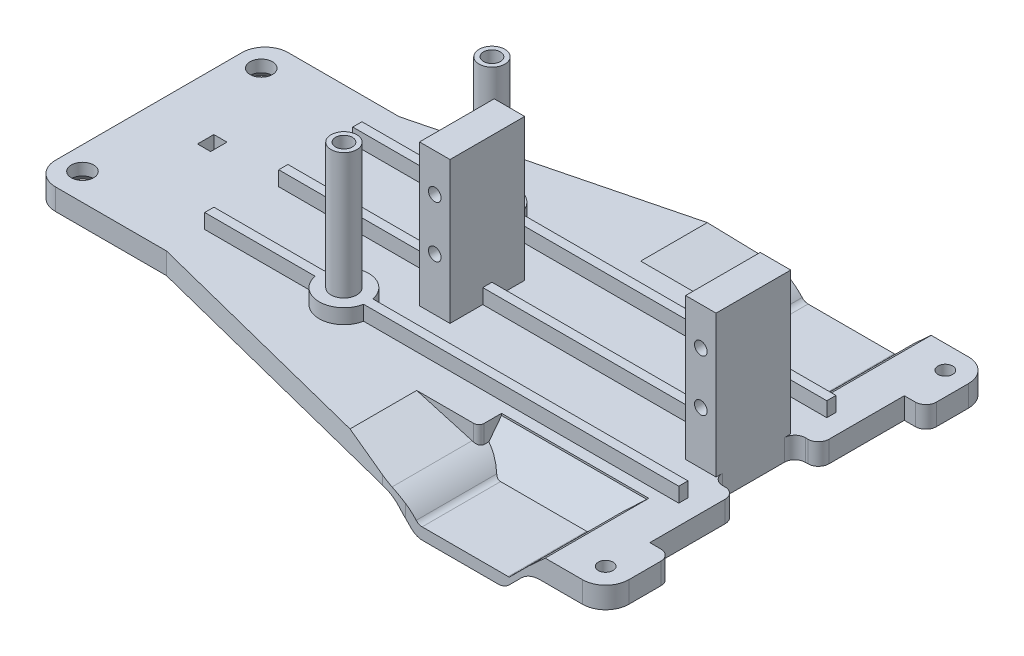
SolidWorks part; units mm, degrees
ref_plane "Front Plane" through (0, 0, 0) normal (0, 0, 1) x (1, 0, 0)
ref_plane "Top Plane" through (0, 0, 0) normal (0, 1, 0) x (1, 0, 0)
ref_plane "Right Plane" through (0, 0, 0) normal (1, 0, 0) x (0, 0, -1)
sketch "Sketch1" plane through (0, 0, 0) normal (0, 1, 0) x (1, 0, 0)
  line L0 (0, 0) -> (0, 17.725)
  line L1 (4.4, 22.125) -> (25.5, 22.125)
  line L2 (25.5, 22.125) -> (83, 36.7)
  line L3 (83, 36.7) -> (119.2, 36.7)
  line L4 (123.6, 32.3) -> (123.6, 26.2)
  line L5 (121.6, 24.2) -> (119.5, 24.2)
  line L6 (119.5, 24.2) -> (119.5, 9.875)
  line L7 (117.5, 7.875) -> (117, 7.875)
  line L8 (115, 5.875) -> (115, 0)
  line L9 (115, 0) -> (0, 0)
  arc A0 (0, 17.725) -> (4.4, 22.125) centre (4.4, 17.725) cw
  arc A1 (119.2, 36.7) -> (123.6, 32.3) centre (119.2, 32.3) cw
  arc A2 (119.5, 9.875) -> (117.5, 7.875) centre (117.5, 9.875) cw
  arc A3 (117, 7.875) -> (115, 5.875) centre (117, 5.875) ccw
  arc A4 (123.6, 26.2) -> (121.6, 24.2) centre (121.6, 26.2) cw
  dimension "D1" = 4.4
  dimension "D3" = 36.7
  dimension "D8" = 2
  dimension "D2" = 123.6
  dimension "D4" = 115
  dimension "D5" = 119.5
  dimension "D6" = 7.875
  dimension "D7" = 24.2
  dimension "D9" = 22.125
  dimension "D10" = 25.5
  dimension "D11" = 83
extrude "Boss-Extrude1" add sketch "Sketch1" along normal blind 4.06
sketch "Sketch2" plane through (0, 0, -36.7) normal (0, 0, -1) x (-1, 0, 0)
  line L0 (-107.5645, -1.4645) -> (-105.2176, -3.8113)
  line L1 (-119.2, 0) -> (-83, 0) construction
  line L2 (-103.0963, -4.69) -> (-88.8, -4.69)
  line L3 (-86.6787, -3.8113) -> (-84.3318, -1.4645)
  line L4 (-95.9481, -4.69) -> (-95.9481, 0) construction
  line L5 (-111.1, 0) -> (-80.7963, 0)
  line L6 (-123.6, 4.06) -> (-123.6, 0) construction
  line L7 (-119.2, 4.06) -> (-83, 4.06) construction
  line L8 (-83, 0) -> (-25.5, 0) construction
  arc A0 (-84.3318, -1.4645) -> (-80.7963, 0) centre (-80.7963, -5) cw
  arc A1 (-107.5645, -1.4645) -> (-111.1, 0) centre (-111.1, -5) ccw
  arc A2 (-88.8, -4.69) -> (-86.6787, -3.8113) centre (-88.8, -1.69) ccw
  arc A3 (-105.2176, -3.8113) -> (-103.0963, -4.69) centre (-103.0963, -1.69) ccw
  point P11 (-84.0806, 0)
  point P14 (-109.0289, 0)
  dimension "D1" = 5
  dimension "D2" = 3
  dimension "D3" = 12.5
  dimension "D4" = 8.75
  dimension "D5" = 34.8
extrude "Boss-Extrude2" add sketch "Sketch2" against normal up to surface (36.7 mm away) up to face at (57.5, 2.03, 0)
sketch "Sketch3" plane through (0, 0, 0) normal (0, 0, 1) x (1, 0, 0)
  line L0 (12.075, 0) -> (12.075, -8.075) construction
  line L2 (15.65, 0) -> (15.65, -8.075)
  line L3 (8.5, 0) -> (8.5, -8.075)
  line L5 (0, 0) -> (80.7963, 0) construction
  line L6 (0, 4.06) -> (0, 0) construction
  arc A0 (15.65, 0) -> (8.5, 0) centre (12.075, 0) ccw
  arc A1 (8.5, -8.075) -> (15.65, -8.075) centre (12.075, -8.075) ccw
  point P4 (12.075, -4.0375)
  point P15 (12.075, -11.65)
  dimension "D1" = 7.15
  dimension "D2" = 11.65
  dimension "D3" = 8.5
extrude "Boss-Extrude3" add sketch "Sketch3" against normal blind 1.555
sketch "Sketch4" plane through (0, 0, -1.555) normal (0, 0, -1) x (-1, 0, 0)
  line L0 (-25.5, 0) -> (-4.4, 0) construction
  line L1 (-10.975, -6.73) -> (-13.175, -6.73)
  line L2 (-9.975, -5.73) -> (-9.975, 0)
  line L3 (-9.975, 0) -> (-14.175, 0)
  line L4 (-14.175, -5.73) -> (-14.175, 0)
  line L5 (-9.975, -6.73) -> (-14.175, 0) construction
  line L6 (-9.975, 0) -> (-14.175, -6.73) construction
  line L7 (-15.65, 0) -> (-8.5, 0) construction
  arc A0 (-13.175, -6.73) -> (-14.175, -5.73) centre (-13.175, -5.73) cw
  arc A1 (-10.975, -6.73) -> (-9.975, -5.73) centre (-10.975, -5.73) ccw
  point P0 (-12.075, -3.365)
  point P7 (-12.075, 0)
  dimension "D3" = 1
  dimension "D1" = 4.2
  dimension "D2" = 6.73
extrude "Boss-Extrude4" add sketch "Sketch4" along normal blind 4.75
fillet "Fillet1" radius 1 5 edges at (14.175, -2.865, -6.305) (13.8821, -6.4371, -6.305) (9.975, -2.865, -6.305) (10.2679, -6.4371, -6.305) (12.075, -6.73, -6.305)
sketch "Sketch5" plane through (0, 0, 0) normal (0, -1, 0) x (1, 0, 0)
  line L0 (111.1, 0) -> (115, 0) construction
  line L1 (0, 0) -> (115, 0) construction
  line L2 (0, -17.725) -> (0, 0) construction
  circle A0 centre (4.4, -17) radius 2.125
  circle A1 centre (119.2, -32.3) radius 1.4
  dimension "D1" = 4.25
  dimension "D2" = 2.8
  dimension "D3" = 32.3
  dimension "D4" = 17
  dimension "D5" = 17
  dimension "D6" = 4.4
extrude "Cut-Extrude1" cut sketch "Sketch5" against normal through all
chamfer "Chamfer1" distance 1.8 angle 45 2 edges at (4.4, 0, -19.125) (119.2, 0, -33.7)
sketch "Sketch6" plane through (0, 0, 0) normal (0, 1, 0) x (1, 0, 0)
  line L3 (80.7963, 36.1414) -> (83, 36.7)
  line L4 (83, 36.7) -> (80.7963, 36.7)
  line L5 (80.7963, 36.7) -> (80.7963, 36.1414)
  line L6 (80.7963, 36.1414) -> (83, 36.7)
  line L7 (83, 36.7) -> (80.7963, 36.7)
  line L8 (80.7963, 36.7) -> (80.7963, 36.1414)
  dimension "D1" = 0
extrude "Cut-Extrude2" cut sketch "Sketch6" against normal blind 4.75
fillet "Fillet2" radius 20 1 edges at (83, 1.7741, -36.7)
sketch "Sketch8" plane through (115, 0, 0) normal (1, 0, 0) x (0, 0, -1)
  line L0 (0, -4.69) -> (36.7, -4.69) construction
  line L1 (0, 0) -> (36.7, 0) construction
  line L2 (0, -4.69) -> (19.8, -4.69)
  line L3 (0, 0) -> (14.7, 0)
  line L4 (0, -4.69) -> (0, 0)
  line L5 (18.6135, -4.1078) -> (15.8865, -0.5822)
  arc A0 (18.6135, -4.1078) -> (19.8, -4.69) centre (19.8, -3.19) ccw
  arc A1 (15.8865, -0.5822) -> (14.7, 0) centre (14.7, -1.5) ccw
  dimension "D1" = 1.5
  dimension "D2" = 14.7
  dimension "D3" = 19.8
extrude "Cut-Extrude3" cut sketch "Sketch8" against normal blind 50
fillet "Fillet3" radius 1 10 edges at (81.8383, -0.1098, -15.2633) (83.7678, -0.9788, -16.1932) (85.5053, -2.6379, -17.4766) (86.8457, -3.9661, -18.5039) (104.0024, -4.5499, -19.167) (105.0506, -3.9661, -18.5039) (110.058, -0.1098, -15.2633) (108.1285, -0.9788, -16.1932) (87.8939, -4.5499, -19.167) (106.391, -2.6379, -17.4766)
ref_plane "Plane1" through (0, 9.6118, -12.4261) normal (0, -0.6118, 0.791) x (1, 0, 0)
sketch "Sketch9" plane through (0, 0, -36.7) normal (0, 0, -1) x (-1, 0, 0)
  line L0 (-112.1, 4.06) -> (-108.8326, 1.075)
  line L1 (-119.2, 4.06) -> (-85.4953, 4.06) construction
  line L2 (-108.8, 1.0439) -> (-105.4126, -2.3436)
  line L3 (-105.059, -2.49) -> (-88.7, -2.49)
  line L4 (-72.26, 4.06) -> (-82.8, 1.0459)
  line L5 (-80.5812, 4.06) -> (-25.5, 4.06) construction
  line L6 (-112.1, 4.06) -> (-72.26, 4.06)
  line L7 (-123.6, 4.06) -> (-123.6, 0) construction
  line L8 (-107.5645, -1.4645) -> (-105.2176, -3.8113) construction
  line L9 (-103.0963, -4.69) -> (-88.8, -4.69) construction
  arc A0 (-82.8, 1.0459) -> (-87.5718, -1.9785) centre (-80.0505, -8.5687) ccw
  arc A1 (-88.7, -2.49) -> (-87.5718, -1.9785) centre (-88.7, -0.99) ccw
  arc A2 (-105.4126, -2.3436) -> (-105.059, -2.49) centre (-105.059, -1.99) ccw
  arc A3 (-108.8326, 1.075) -> (-108.8, 1.0439) centre (-109.5071, 0.3368) cw
  dimension "D1" = 1.5
  dimension "D2" = 0.5
  dimension "D3" = 1
  dimension "D10" = 10
  dimension "D4" = 11.5
  dimension "D5" = 0.9
  dimension "D6" = 14.8
  dimension "D7" = 2.2
  dimension "D8" = 51.34
  dimension "D9" = 40.8
  dimension "D11" = 34.9
extrude "Cut-Extrude4" cut sketch "Sketch9" against normal up to surface (19.9795 mm away) up to plane "Plane1"
sketch "Sketch10" plane through (0, 4.06, 0) normal (0, 1, 0) x (1, 0, 0)
  line L0 (84.1, 17) -> (84.1, 20.3)
  line L1 (72.26, 16.7205) -> (112.1, 16.7205) construction
  line L2 (83.1, 21.3) -> (72.26, 21.3)
  line L3 (72.26, 16.7205) -> (72.26, 33.9776) construction
  line L4 (72.26, 21.3) -> (72.26, 16.7205)
  line L5 (72.26, 16.7205) -> (84.1, 16.7205)
  line L6 (123.6, 26.2) -> (123.6, 32.3) construction
  line L8 (0, 0) -> (115, 0) construction
  line L9 (112.1, 17) -> (112.1, 16.7205)
  line L10 (112.1, 16.7205) -> (112.1, 36.7) construction
  line L11 (112.1, 16.7205) -> (84.1, 16.7205)
  line L12 (84.1, 17) -> (112.1, 17)
  arc A0 (84.1, 20.3) -> (83.1, 21.3) centre (83.1, 20.3) ccw
  dimension "D1" = 1
  dimension "D2" = 39.5
  dimension "D3" = 21.3
  dimension "D4" = 17
extrude "Boss-Extrude5" add sketch "Sketch10" against normal up to body separate body
sketch "Sketch11" plane through (0, 0, 0) normal (0, 0, 1) x (1, 0, 0)
  line L0 (115, 4.06) -> (115, 0) construction
  line L14 (0, 4.06) -> (115, 4.06) construction
  line L15 (58.6, 4.06) -> (64.4, 4.06)
  line L16 (58.6, 4.06) -> (58.6, 31.06)
  line L17 (58.6, 31.06) -> (64.4, 31.06)
  line L18 (64.4, 4.06) -> (64.4, 31.06)
  line L20 (109.2, 4.06) -> (115, 4.06)
  line L21 (109.2, 4.06) -> (109.2, 31.06)
  line L22 (109.2, 31.06) -> (115, 31.06)
  line L23 (115, 4.06) -> (115, 31.06)
  dimension "D1" = 5.8
  dimension "D2" = 27
  dimension "D3" = 56.4
extrude "Boss-Extrude6" add sketch "Sketch11" against normal blind 7.1
sketch "Sketch12" plane through (0, 0, -7.1) normal (0, 0, -1) x (-1, 0, 0)
  line L0 (-115, 31.06) -> (-109.2, 31.06) construction
  line L1 (-64.4, 31.06) -> (-58.6, 31.06) construction
  line L2 (-119.2, 4.06) -> (-112.1, 4.06) construction
  circle A0 centre (-112.1, 23.86) radius 1.2
  circle A1 centre (-112.1, 14.06) radius 1.2
  circle A2 centre (-61.5, 23.86) radius 1.2
  circle A3 centre (-61.5, 14.06) radius 1.2
  point P8 (-61.5, 31.06)
  point P10 (-112.1, 31.06)
  dimension "D3" = 2.4
  dimension "D1" = 9.8
  dimension "D2" = 10
extrude "Cut-Extrude5" cut sketch "Sketch12" against normal through all
sketch "Sketch13" plane through (0, 4.06, 0) normal (0, 1, 0) x (1, 0, 0)
  line L2 (0, 0) -> (58.6, 0) construction
  line L3 (123.6, 26.2) -> (123.6, 32.3) construction
  circle A0 centre (51.2, 14.075) radius 4.7
  dimension "D1" = 9.4
  dimension "D2" = 72.4
  dimension "D3" = 14.075
extrude "Boss-Extrude7" add sketch "Sketch13" along normal blind 2.8
sketch "Sketch14" plane through (0, 6.86, 0) normal (0, 1, 0) x (1, 0, 0)
  circle A0 centre (51.2, 14.075) radius 2.45
extrude "Boss-Extrude8" add sketch "Sketch14" along normal offset from surface (23.95 mm away) 26.75 up to face at (51.2, 4.06, -18.775) offset beyond the face yes
sketch "Sketch15" plane through (0, 30.81, 0) normal (0, 1, 0) x (1, 0, 0)
  circle A0 centre (51.2, 14.075) radius 1.6
extrude "Cut-Extrude6" cut sketch "Sketch15" against normal blind 25
sketch "Sketch16" plane through (0, 6.86, 0) normal (0, 1, 0) x (1, 0, 0)
  line L0 (115.75, 14.075) -> (25.6, 14.075)
  line L1 (119.5, 9.875) -> (119.5, 24.2) construction
  point P4 (51.2, 14.075)
  dimension "D1" = 90.15
  dimension "D2" = 3.75
extrude "Extrude-Thin1" add sketch "Sketch16" against normal up to surface (2.8 mm away) thin up to face at (51.2, 4.06, -18.775) thin type mid plane wall 1.75
sketch "Sketch17" plane through (0, 6.86, 0) normal (0, 1, 0) x (1, 0, 0)
  line L0 (115, 0) -> (25.6, 0)
  line L1 (0, 0) -> (58.6, 0) construction
  line L2 (25.6, 13.2) -> (25.6, 14.95) construction
extrude "Extrude-Thin2" add sketch "Sketch17" against normal up to surface (2.8 mm away) thin contours L0 up to face at (60.9375, 4.06, -14.075) thin type one direction wall 0.875
sketch "Sketch18" plane through (0, 0, 0) normal (0, 0, 1) x (1, 0, 0)
  line L0 (0, 4.06) -> (25.6, 4.06) construction
  line L1 (10.825, 4.06) -> (13.325, 4.06)
  line L2 (10.825, 4.06) -> (10.825, -9.325)
  line L3 (10.825, -9.325) -> (13.325, -9.325)
  line L4 (13.325, 4.06) -> (13.325, -9.325)
  line L5 (10.825, -9.325) -> (12.075, -8.075) construction
  line L6 (12.075, -8.075) -> (13.325, -9.325) construction
  point P0 (12.075, -8.075)
  dimension "D1" = 2.5
extrude "Cut-Extrude7" cut sketch "Sketch18" against normal up to surface (1.555 mm away) up to face at (12.075, -4.5059, -1.555)
mirror "Mirror1" about plane through (115, 4.06, 0) normal (0, 0, -1) of bodies 117
